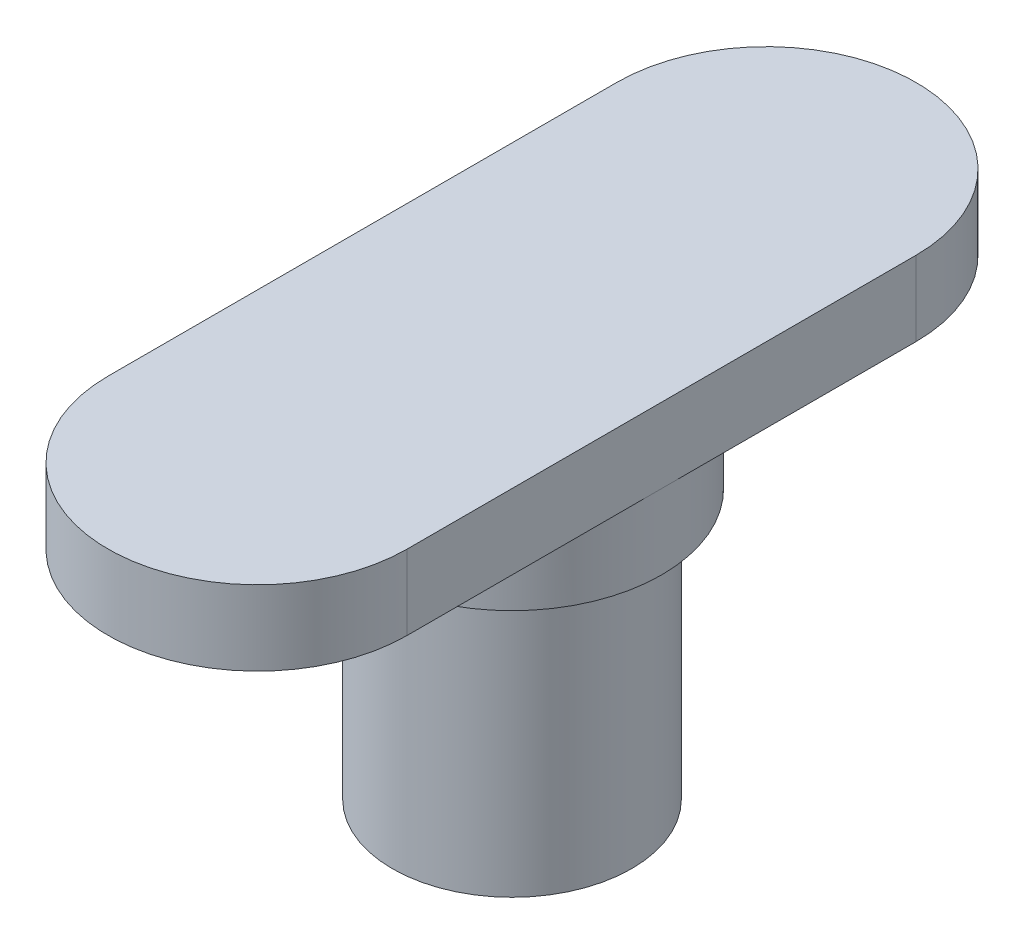
SolidWorks part; units mm, degrees
ref_plane "Front Plane" through (0, 0, 0) normal (0, 0, 1) x (1, 0, 0)
ref_plane "Top Plane" through (0, 0, 0) normal (0, 1, 0) x (1, 0, 0)
ref_plane "Right Plane" through (0, 0, 0) normal (1, 0, 0) x (0, 0, -1)
sketch "Sketch3" plane through (0, 0, 0) normal (0, 1, 0) x (1, 0, 0)
  line L0 (0, -8.5) -> (0, 8.5) construction
  line L1 (-5, -8.5) -> (-5, 8.5)
  line L2 (5, -8.5) -> (5, 8.5)
  circle A0 centre (0, 0) radius 4
  circle A1 centre (0, 0) radius 5
  arc A2 (-5, -8.5) -> (5, -8.5) centre (0, -8.5) ccw
  arc A3 (5, 8.5) -> (-5, 8.5) centre (0, 8.5) ccw
  point P6 (0, 0)
  dimension "D1" = 8
  dimension "D2" = 10
  dimension "D3" = 17
extrude "Boss-Extrude1" add sketch "Sketch3" along normal blind 9 contours A0
extrude "Boss-Extrude2" add sketch "Sketch3<3>" along normal blind 5 from surface contours A1 starting at face at (0, 9, 4)
sketch "Sketch3<3>" plane through (0, 0, 0) normal (0, 1, 0) x (1, 0, 0) same geometry as "Sketch3"
extrude "Boss-Extrude3" add sketch "Sketch3<5>" against normal blind 2.5 from surface contours L1 A3 L2 A2 starting at face at (0, 14, 5)
sketch "Sketch3<5>" plane through (0, 0, 0) normal (0, 1, 0) x (1, 0, 0) same geometry as "Sketch3"
sketch "Sketch5" plane through (0, 0, 0) normal (0, 1, 0) x (1, 0, 0)
  circle A0 centre (0, 0) radius 2.5
  dimension "D1" = 5
extrude "Cut-Extrude1" cut sketch "Sketch5" along normal offset from surface (11 mm away) 3 contours A0 region at (0, 0, 0) up to face at (0, 14, 0)
thread "Thread1" pitch 0.8 method cut profile "Thread Profile1" start angle 0, offset 1, length 0, pitch 0.8, diameter 5
ref_plane "Plane1" through (2.5, -1, 0) normal (0, 0, 1) x (1, 0, 0)
sketch "Thread Profile1" plane through (2.5, -1, 0) normal (0, 0, 1) x (1, 0, 0)
  line L0 (0, 0) -> (0, 0.8) construction
  line L1 (0, 0) -> (0.433, 0.25)
  line L2 (0.433, 0.25) -> (0.433, 0.35)
  line L3 (0.433, 0.35) -> (0, 0.6)
  line L4 (0.433, 0.3) -> (0, 0.3) construction
  line L11 (0, 0) -> (0, 0.6)
  point P2 (0, 0)
  dimension "Pitch" = 0.8
  dimension "Profile_Angle" = 60
  dimension "Profile_Land" = 0.1
  dimension "Profile_Height" = 0.433
